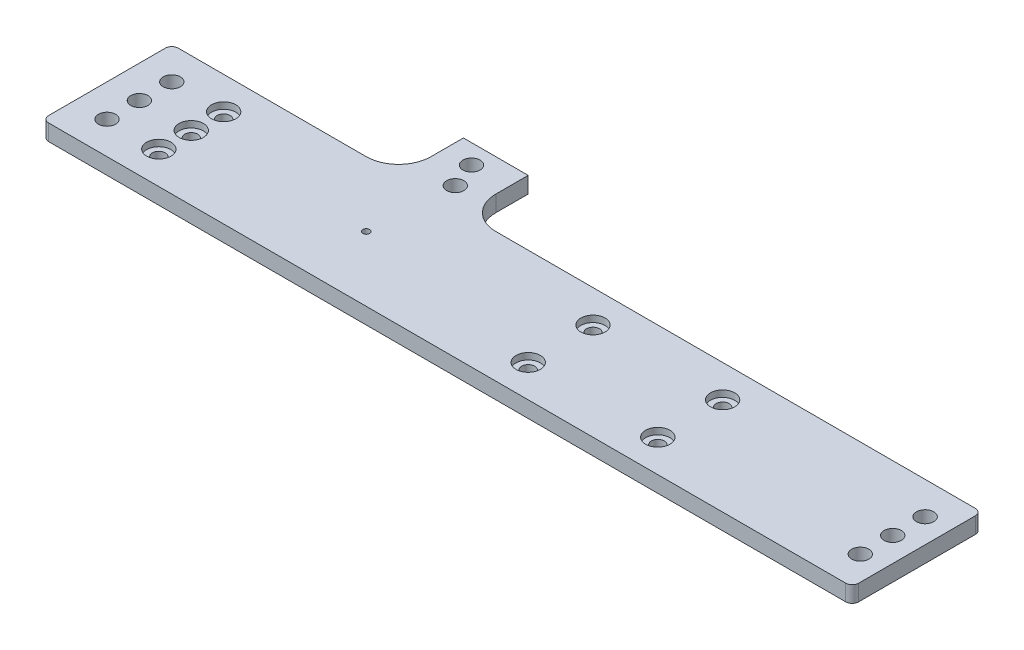
SolidWorks part; units mm, degrees
material "6061-T6 (SS)"
ref_plane "Front" through (0, 0, 0) normal (0, 0, 1) x (1, 0, 0)
ref_plane "Top" through (0, 0, 0) normal (0, 1, 0) x (1, 0, 0)
ref_plane "Right" through (0, 0, 0) normal (1, 0, 0) x (0, 0, -1)
sketch "Sketch1" plane through (0, 0, 0) normal (0, 1, 0) x (1, 0, 0)
  line L1 (-158.75, -25.4) -> (158.75, -25.4)
  line L2 (-158.75, -25.4) -> (-158.75, 25.4)
  line L3 (-158.75, 25.4) -> (158.75, 25.4)
  line L4 (158.75, -25.4) -> (158.75, 25.4)
  line L5 (-158.75, -25.4) -> (158.75, 25.4) construction
  line L6 (-158.75, 25.4) -> (158.75, -25.4) construction
  point P0 (0, 0)
  dimension "D1" = 50.8
  dimension "D2" = 317.5
extrude "Boss-Extrude1" add sketch "Sketch1" along normal blind 6.35
hole_wizard "CBORE for #10 Socket Head Cap Screw1" positions "Sketch2" profile "Sketch4" counterbore size "#10" standard "ANSI Inch" end condition through all
sketch "Sketch2" plane through (0, 6.35, 0) normal (0, 1, 0) x (1, 0, 0)
  line L2 (158.75, 25.4) -> (-158.75, 25.4) construction
  line L6 (-158.75, -25.4) -> (158.75, -25.4) construction
  line L8 (-158.75, 25.4) -> (-158.75, -25.4) construction
  line L12 (158.75, -25.4) -> (158.75, 25.4) construction
  line L15 (19.05, 12.7) -> (19.05, 25.4) construction
  line L17 (19.05, -12.7) -> (19.05, -25.4) construction
  line L18 (-125.73, -25.4) -> (-125.73, -12.7) construction
  line L20 (-125.73, 0) -> (-125.73, 12.7) construction
  line L21 (-125.73, 12.7) -> (-125.73, 25.4) construction
  line L22 (-125.73, 0) -> (-125.73, -12.7) construction
  point P64 (19.05, 12.7)
  point P66 (69.85, 12.7)
  point P68 (19.05, -12.7)
  point P70 (69.85, -12.7)
  point P92 (-125.73, 12.7)
  point P94 (-125.73, 0)
  point P102 (-125.73, -12.7)
  dimension "D2" = 50.8
  dimension "D3" = 25.4
  dimension "D4" = 88.9
  dimension "D5" = 33.02
sketch "Sketch4" plane through (-125.73, 6.35, 12.7) normal (1, 0, 0) x (0, 0, 1)
  line L0 (0, 0) -> (0, 6.35)
  line L1 (0, 6.35) -> (2.5527, 6.35)
  line L3 (2.5527, 6.35) -> (2.5527, 2.54)
  line L4 (2.5527, 2.54) -> (4.7625, 2.54)
  line L5 (4.7625, 2.54) -> (4.7625, 0)
  line L7 (4.7625, 0) -> (0, 0)
  line L11 (0, -6.35) -> (0, 107.95) construction
  dimension "Thru Hole Dia." = 5.1054
  dimension "Thru Hole Depth" = 6.35
  dimension "C'Bore Dia." = 9.525
  dimension "C'Bore Depth" = 2.54
sketch "Sketch7" plane through (0, 0, 0) normal (0, -1, 0) x (1, 0, 0)
  line L0 (-146.05, 25.4) -> (-146.05, 12.7) construction
  line L1 (-158.75, 25.4) -> (158.75, 25.4) construction
  line L2 (-146.05, 12.7) -> (-146.05, 0) construction
  line L3 (-146.05, 0) -> (-146.05, -12.7) construction
  line L4 (-146.05, -12.7) -> (-146.05, -25.4) construction
  line L5 (158.75, -25.4) -> (-158.75, -25.4) construction
  line L7 (-158.75, -25.4) -> (-158.75, 25.4) construction
  line L8 (149.225, 25.4) -> (149.225, 12.7) construction
  line L9 (149.225, 12.7) -> (149.225, 0) construction
  line L10 (149.225, 0) -> (149.225, -12.7) construction
  line L11 (149.225, -12.7) -> (149.225, -25.4) construction
  line L13 (158.75, 25.4) -> (158.75, -25.4) construction
  point P0 (-146.05, 12.7)
  point P2 (-146.05, 0)
  point P4 (-146.05, -12.7)
  point P6 (149.225, 12.7)
  point P8 (149.225, 0)
  point P10 (149.225, -12.7)
  dimension "D1" = 12.7
  dimension "D2" = 9.525
hole_wizard "1/4 Clearance Hole2" positions "Sketch7" profile "Sketch6" hole size "1/4" standard "ANSI Inch" end condition through all
sketch "Sketch6" plane through (-146.05, 0, 12.7) normal (1, 0, 0) x (0, 0, -1)
  line L0 (0, 0) -> (0, 6.35)
  line L1 (0, 6.35) -> (3.3782, 6.35)
  line L2 (3.3782, 6.35) -> (3.3782, 0)
  line L5 (3.3782, 0) -> (0, 0)
  line L11 (0, -6.35) -> (0, 107.95) construction
  dimension "Thru Hole Dia." = 6.7564
  dimension "Thru Hole Depth" = 6.35
sketch "Sketch10" plane through (0, 0, 0) normal (0, -1, 0) x (-1, 0, 0)
  line L0 (158.75, 25.4) -> (158.75, -25.4) construction
  point P0 (57.15, 0)
  dimension "D1" = 101.6
hole_wizard "#6-32 Tapped Hole1" positions "Sketch10" profile "Sketch9" tap size "#6-32" standard "ANSI Inch" end condition through all
sketch "Sketch9" plane through (-57.15, 0, 0) normal (1, 0, 0) x (0, 0, -1)
  line L0 (0, 0) -> (0, 6.35)
  line L1 (0, 6.35) -> (1.3525, 6.35)
  line L2 (1.3525, 6.35) -> (1.3525, 0)
  line L5 (1.3525, 0) -> (0, 0)
  line L11 (0, -6.35) -> (0, 107.95) construction
  dimension "Thru Tap Drill Dia." = 2.7051
  dimension "Thru Tap Drill Depth" = 6.35
cosmetic thread "Hole Thread1" parameters "D2"=3.5052
sketch "Sketch11" plane through (0, 0, 0) normal (0, -1, 0) x (1, 0, 0)
  line L0 (158.75, -25.4) -> (-158.75, -25.4) construction
  line L1 (-70.0118, -25.4) -> (-48.1024, -25.4)
  line L2 (-70.0118, -25.4) -> (-70.0118, -45.81)
  line L3 (-70.0118, -45.81) -> (-48.1024, -45.81)
  line L4 (-48.1024, -25.4) -> (-48.1024, -45.81)
extrude "Boss-Extrude2" [suppressed] add sketch "Sketch11" against normal up to surface (6.35 mm away) up to face at (-57.15, 6.35, -1.3526)
sketch "Sketch12" plane through (0, 6.35, 0) normal (0, 1, 0) x (1, 0, 0)
  line L5 (-158.75, 25.4) -> (-158.75, -25.4) construction
  line L6 (-69.85, 25.4) -> (-69.85, 50.8)
  line L7 (158.75, 25.4) -> (-158.75, 25.4) construction
  line L8 (-69.85, 50.8) -> (-44.45, 50.8)
  line L9 (-44.45, 50.8) -> (-44.45, 25.4)
  line L10 (-69.85, 25.4) -> (-44.45, 25.4)
  dimension "D4" = 88.9
  dimension "D5" = 25.4
  dimension "D6" = 25.4
extrude "Boss-Extrude3" add sketch "Sketch12" against normal up to surface (6.35 mm away) up to face at (-57.15, 0, -1.3526)
sketch "Sketch15" plane through (0, 0, 0) normal (0, -1, 0) x (-1, 0, 0)
  point P0 (59.055, 43.18)
  point P3 (55.245, 33.02)
hole_wizard "1/4 Clearance Hole1" positions "Sketch15" profile "Sketch14" hole size "1/4" standard "ANSI Inch" end condition through all
sketch "Sketch14" plane through (-59.055, 0, -43.18) normal (1, 0, 0) x (0, 0, -1)
  line L0 (0, 0) -> (0, 6.35)
  line L1 (0, 6.35) -> (3.3782, 6.35)
  line L2 (3.3782, 6.35) -> (3.3782, 0)
  line L5 (3.3782, 0) -> (0, 0)
  line L11 (0, -6.35) -> (0, 107.95) construction
  dimension "Thru Hole Dia." = 6.7564
  dimension "Thru Hole Depth" = 6.35
fillet "Fillet1" radius 12.7 2 edges at (-44.45, 3.175, -25.4) (-69.85, 3.175, -25.4)
fillet "Fillet2" radius 2.54 4 edges at (158.75, 3.175, -25.4) (158.75, 3.175, 25.4) (-158.75, 3.175, 25.4) (-158.75, 3.175, -25.4)
